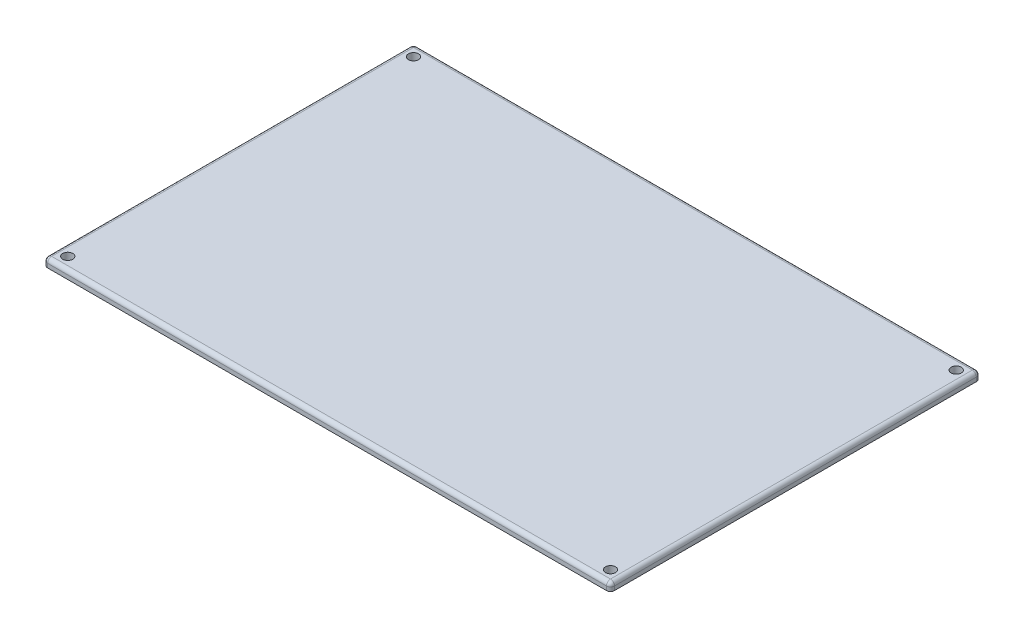
SolidWorks part; units mm, degrees
ref_plane "Front Plane" through (0, 0, 0) normal (0, 0, 1) x (1, 0, 0)
ref_plane "Top Plane" through (0, 0, 0) normal (0, 1, 0) x (1, 0, 0)
ref_plane "Right Plane" through (0, 0, 0) normal (1, 0, 0) x (0, 0, -1)
sketch "Sketch1" plane through (0, 0, 0) normal (0, 1, 0) x (1, 0, 0)
  line L1 (0, 0) -> (141, 0)
  line L2 (0, 0) -> (0, 92)
  line L3 (0, 92) -> (141, 92)
  line L4 (141, 0) -> (141, 92)
extrude "Boss-Extrude1" add sketch "Sketch1" along normal blind 2
sketch "Sketch2" plane through (0, 0, 0) normal (0, -1, 0) x (1, 0, 0)
  circle A0 centre (3, -3) radius 1.26
  circle A1 centre (138, -3) radius 1.26
  circle A2 centre (138, -89) radius 1.26
  circle A3 centre (3, -89) radius 1.26
extrude "Cut-Extrude1" cut sketch "Sketch2" against normal blind 10
fillet "Fillet1" radius 1 4 edges at (141, 2, -46) (70.5, 2, -92) (0, 2, -46) (70.5, 2, 0)
shell "Shell1" thickness 1.5 removed face at (3, 0, -87.74)
fillet "Fillet2" radius 1 8 edges at (0.2929, 1.7071, -0.2929) (140.7071, 1.7071, -0.2929) (140.7071, 1.7071, -91.7071) (0.2929, 1.7071, -91.7071) (0, 0.5, 0) (141, 0.5, 0) (141, 0.5, -92) (0, 0.5, -92)
